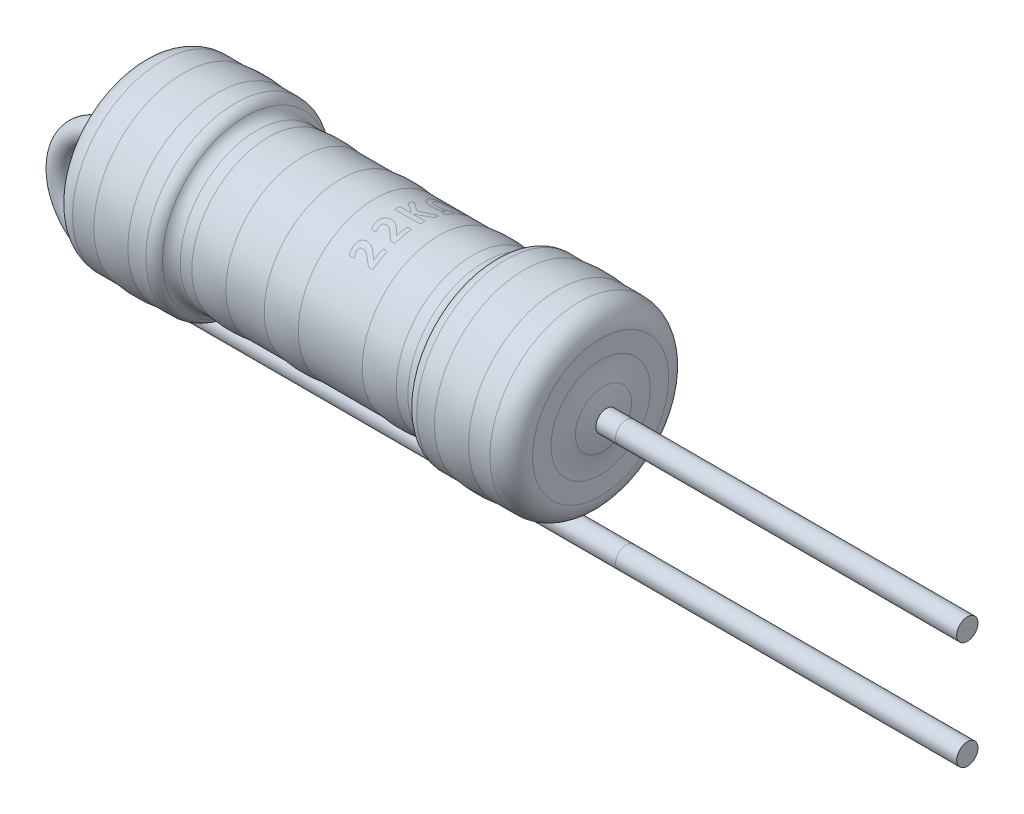
SolidWorks part; units mm, degrees
ref_plane "Front Plane" through (0, 0, 0) normal (0, 0, 1) x (1, 0, 0)
ref_plane "Top Plane" through (0, 0, 0) normal (0, 1, 0) x (1, 0, 0)
ref_plane "Right Plane" through (0, 0, 0) normal (1, 0, 0) x (0, 0, -1)
sketch "Sketch Set Wire Width" plane through (0, 0, 0) normal (0, 0, 1) x (1, 0, 0)
  line L0 (0, 0) -> (6, 0)
  line L1 (6, -2.54) -> (-6, -2.54)
  line L2 (6, 0) -> (14.0102, 0)
  line L3 (-6, 0) -> (-6, -2.54) construction
  line L4 (-6, 0) -> (-6, -2.54) construction
  line L5 (6, -2.54) -> (6, 0) construction
  line L6 (6, -2.54) -> (14.0102, -2.54)
  line L7 (14.0102, -2.54) -> (14.0102, 0) construction
  line L8 (-6, 0) -> (0, 0)
  arc A0 (-6, 0) -> (-6, -2.54) centre (-6, -1.27) ccw
  dimension "D2" = 2.54
  dimension "D3" = 30
  dimension "D1" = 12
  dimension "D4" = 6
sketch "Sketch Wire Diameter" plane through (0, 0, 0) normal (1, 0, 0) x (0, 0, -1)
  circle A0 centre (0, 0) radius 0.25
  dimension "D1" = 0.5
sweep "SET WIRE LENGTH" add profiles "Sketch Wire Diameter" path "Sketch Set Wire Width"
sketch "Sketch3" plane through (0, 0, 0) normal (0, 0, 1) x (1, 0, 0)
  line L0 (-5.4, 0) -> (5.4, 0)
  line L1 (0, 0) -> (0, 1.8) construction
  line L2 (-2.9, 1.8) -> (2.9, 1.8)
  line L3 (-5.4, 0) -> (-5.4, 1.6)
  line L4 (-4.9, 2.1) -> (-3.18, 2.1)
  line L5 (-2.9, 1.82) -> (-2.9, 1.8)
  line L6 (5.4, 0) -> (5.4, 1.6)
  line L7 (4.9, 2.1) -> (3.18, 2.1)
  line L8 (2.9, 1.82) -> (2.9, 1.8)
  arc A0 (-5.4, 1.6) -> (-4.9, 2.1) centre (-4.9, 1.6) cw
  arc A1 (5.4, 1.6) -> (4.9, 2.1) centre (4.9, 1.6) ccw
  arc A2 (-3.18, 2.1) -> (-2.9, 1.82) centre (-3.18, 1.82) cw
  arc A3 (3.18, 2.1) -> (2.9, 1.82) centre (3.18, 1.82) ccw
  dimension "D5" = 0.5
  dimension "D6" = 0.28
  dimension "D1" = 10.8
  dimension "D2" = 5.8
  dimension "D3" = 1.8
  dimension "D4" = 2.1
revolve "Revolve2" add sketch "Sketch3" angle 360 about L0
fillet "Fillet1" radius 0.3 2 edges at (2.9, 0, 1.8) (-2.9, 0, 1.8)
sketch "Sketch5" plane through (0, 0, 0) normal (0, 0, 1) x (1, 0, 0)
  line L0 (0, 0) -> (2, 0) construction
  line L1 (0, 0) -> (-0.3, 0) construction
  line L2 (-0.3, 0) -> (-2, 0) construction
  line L3 (-2, 0) -> (-4, 0) construction
  line L4 (2, 0) -> (4, 0) construction
  line L5 (-4, 0) -> (-4, 2.1) construction
  line L6 (-0.3, 0) -> (-0.3, 1.8) construction
  line L7 (-2, 0) -> (-2, 1.8) construction
  line L8 (2, 0) -> (2, 1.8) construction
  line L9 (4, 0) -> (4, 2.1) construction
  line L10 (-4, 2.1) -> (-4, 2.13) construction
  line L11 (-4.9, 2.1) -> (-3.18, 2.1) construction
  line L12 (4.9, 2.1) -> (3.18, 2.1) construction
  line L13 (-2.9, 1.8) -> (2.9, 1.8) construction
  line L14 (-2, 1.8) -> (-2, 1.83) construction
  line L17 (-4.4, 2.1) -> (-3.6, 2.1)
  line L19 (-5.4, 0) -> (5.4, 0) construction
  line L22 (-2.4, 1.8) -> (-1.6, 1.8) construction
  line L26 (-0.7, 1.8) -> (0.1, 1.8) construction
  line L30 (1.6, 1.8) -> (2.4, 1.8) construction
  line L34 (3.6, 2.1) -> (4.4, 2.1) construction
  line L36 (-0.3, 1.8) -> (-0.3, 1.83) construction
  line L37 (2, 1.8) -> (2, 1.83) construction
  line L38 (4, 2.1) -> (4, 2.13) construction
  arc A0 (-4.4, 2.1) -> (-3.6, 2.1) centre (-4, -0.5517) cw
  arc A1 (-2.4, 1.8) -> (-1.6, 1.8) centre (-2, -0.8517) cw construction
  arc A2 (-0.7, 1.8) -> (0.1, 1.8) centre (-0.3, -0.8517) cw construction
  arc A3 (1.6, 1.8) -> (2.4, 1.8) centre (2, -0.8517) cw construction
  arc A4 (3.6, 2.1) -> (4.4, 2.1) centre (4, -0.5517) cw construction
  dimension "D3" = 0.8
  dimension "D1" = 4
  dimension "D2" = 4
  dimension "D4" = 0.03
  dimension "D5" = 2
  dimension "D6" = 2
  dimension "D7" = 1.7
revolve "Band 1" add sketch "Sketch5" angle 360 about L2
sketch "Sketch8" plane through (0, 0, 0) normal (0, 0, 1) x (1, 0, 0)
  line L0 (-2.4, 1.8) -> (-1.6, 1.8) construction
  line L1 (-2.4, 1.8) -> (-1.6, 1.8)
  arc A0 (-1.6, 1.8) -> (-2.4, 1.8) centre (-2, -0.8517) ccw construction
  arc A1 (-1.6, 1.8) -> (-2.4, 1.8) centre (-2, -0.8517) ccw
revolve "Band 2" add sketch "Sketch8" angle 360 about L2
sketch "Sketch9" plane through (0, 0, 0) normal (0, 0, 1) x (1, 0, 0)
  line L0 (-0.7, 1.8) -> (0.1, 1.8) construction
  line L1 (-0.7, 1.8) -> (0.1, 1.8)
  arc A0 (0.1, 1.8) -> (-0.7, 1.8) centre (-0.3, -0.8517) ccw construction
  arc A1 (0.1, 1.8) -> (-0.7, 1.8) centre (-0.3, -0.8517) ccw
revolve "Band 3" add sketch "Sketch9" angle 360 about L2
sketch "Sketch10" plane through (0, 0, 0) normal (0, 0, 1) x (1, 0, 0)
  line L0 (1.6, 1.8) -> (2.4, 1.8) construction
  line L1 (1.6, 1.8) -> (2.4, 1.8)
  arc A0 (2.4, 1.8) -> (1.6, 1.8) centre (2, -0.8517) ccw construction
  arc A1 (2.4, 1.8) -> (1.6, 1.8) centre (2, -0.8517) ccw
revolve "Band 4" add sketch "Sketch10" angle 360 about L0
sketch "Sketch11" plane through (0, 0, 0) normal (0, 0, 1) x (1, 0, 0)
  line L0 (3.6, 2.1) -> (4.4, 2.1) construction
  line L1 (3.6, 2.1) -> (4.4, 2.1)
  arc A0 (4.4, 2.1) -> (3.6, 2.1) centre (4, -0.5517) ccw construction
  arc A1 (4.4, 2.1) -> (3.6, 2.1) centre (4, -0.5517) ccw
revolve "Band 5" add sketch "Sketch11" angle 360 about L4
sketch "Sketch12" plane through (0, 0, 0) normal (0, 0, 1) x (1, 0, 0)
  line L0 (-5.35, 0) -> (5.35, 0) construction
  line L1 (-5.35, 1) -> (-5.35, 0)
  line L2 (5.35, 1) -> (5.35, 0)
  line L3 (-5.35, 0) -> (-5.55, 0)
  line L4 (5.35, 0) -> (5.55, 0)
  arc A0 (-5.35, 1) -> (-5.55, 0) centre (-2.95, 0) ccw
  arc A1 (5.35, 1) -> (5.55, 0) centre (2.95, 0) cw
  dimension "D3" = 0.2
  dimension "D4" = 2.6
  dimension "D1" = 10.7
  dimension "D2" = 1
revolve "Revolve10" add sketch "Sketch12" angle 360 about L0
fillet "Fillet2" radius 2 2 edges at (5.4, 0, 0.8703) (-5.4, 0, -0.8703)
ref_plane "Plane2" through (0, 3, 0) normal (0, 1, 0) x (1, 0, 0)
sketch "Sketch13" plane through (0, 3, 0) normal (0, 1, 0) x (1, 0, 0)
  line L0 (0, 0) -> (1.15, 0) construction
  line L1 (1.15, 1.75) -> (1.15, -1.75) construction
  text T0 "22KΩ" font "Calibri" height 0.6
  dimension "D1" = 3.5
  dimension "D2" = 1.15
wrap "Wrap1" sketch "Sketch13" wrap type scribe source sketch "Sketch13" face at (0.1, 1.8, 0)
